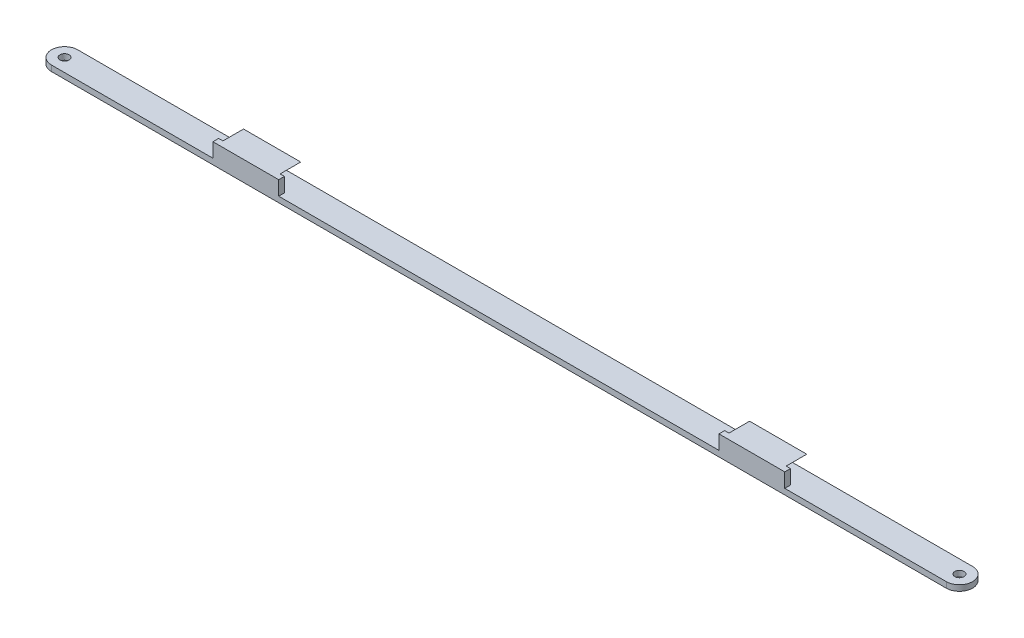
SolidWorks part; units mm, degrees
material "PLA"
ref_plane "Спереди" through (0, 0, 0) normal (0, 0, 1) x (1, 0, 0)
ref_plane "Сверху" through (0, 0, 0) normal (0, 1, 0) x (1, 0, 0)
ref_plane "Справа" through (0, 0, 0) normal (1, 0, 0) x (0, 0, -1)
sketch "Эскиз1" plane through (0, 0, 0) normal (0, 1, 0) x (1, 0, 0)
  line L0 (0, 0) -> (0, 44955.4742) construction
  line L1 (0, 0) -> (-44955.4742, 0) construction
  line L2 (-156.5, 4.6) -> (156.5, 4.6)
  line L3 (156.5, -4.6) -> (-156.5, -4.6)
  circle A0 centre (-156.5, 0) radius 1.6
  circle A1 centre (156.5, 0) radius 1.6
  arc A2 (-156.5, 4.6) -> (-156.5, -4.6) centre (-156.5, 0) ccw
  arc A3 (156.5, 4.6) -> (156.5, -4.6) centre (156.5, 0) cw
  circle A5 centre (-156.5, 0) radius 4.6 construction
  point P17 (-152.1966, 1.3157)
  dimension "D2" = 3.2
  dimension "D1" = 313
  dimension "D3" = 3
extrude "Бобышка-Вытянуть1" add sketch "Эскиз1" along normal blind 2
sketch "Эскиз2" plane through (0, 0, 4.6) normal (0, 0, 1) x (1, 0, 0)
  line L0 (0, 0) -> (0, 50000) construction
  line L1 (-156.5, 0) -> (156.5, 0) construction
  line L3 (-156.5, 2) -> (156.5, 2) construction
  line L7 (-93.5, 2) -> (-98.5, 7)
  line L8 (-98.5, 7) -> (-78.5, 7)
  line L9 (-78.5, 7) -> (-83.5, 2)
  line L10 (-83.5, 2) -> (-93.5, 2)
  line L11 (78.5, 7) -> (83.5, 2)
  line L12 (98.5, 7) -> (78.5, 7)
  line L13 (93.5, 2) -> (98.5, 7)
  line L14 (83.5, 2) -> (93.5, 2)
  point P4 (0, 0)
  point P12 (0, 2)
  dimension "D1" = 20
  dimension "D2" = 5
  dimension "D3" = 10
  dimension "D4" = 83.5
extrude "Бобышка-Вытянуть3" add sketch "Эскиз2" against normal up to surface (9.2 mm away) up to face at (0, 1, -4.6)
sketch "Эскиз3" plane through (0, 0, 4.6) normal (0, 0, 1) x (1, 0, 0)
  line L0 (-156.5, 0) -> (156.5, 0) construction
  line L1 (-100, 0) -> (-77, 0)
  line L2 (-100, 0) -> (-100, 7)
  line L3 (-100, 7) -> (-77, 7)
  line L4 (-77, 0) -> (-77, 7)
  line L6 (0, 0) -> (0, 50000) construction
  line L7 (100, 7) -> (77, 7)
  line L8 (77, 0) -> (77, 7)
  line L9 (100, 0) -> (77, 0)
  line L10 (100, 0) -> (100, 7)
  point P12 (0, 0)
  dimension "D2" = 1.5
  dimension "D3" = 1.5
extrude "Бобышка-Вытянуть4" add sketch "Эскиз3" against normal blind 2
